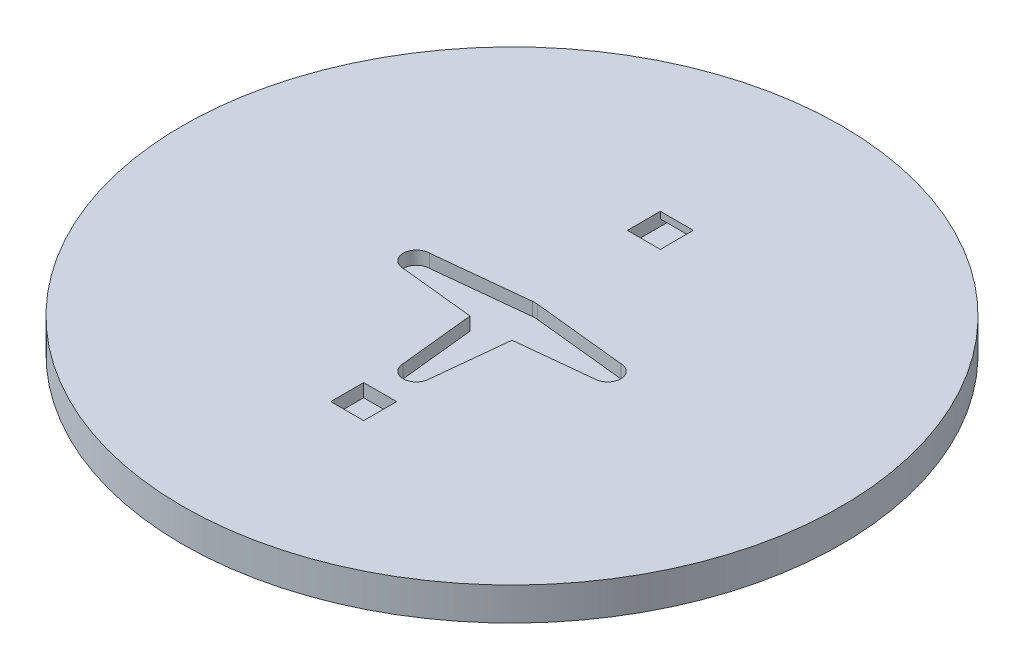
SolidWorks part; units mm, degrees
ref_plane "Front Plane" through (0, 0, 0) normal (0, 0, 1) x (1, 0, 0)
ref_plane "Top Plane" through (0, 0, 0) normal (0, 1, 0) x (1, 0, 0)
ref_plane "Right Plane" through (0, 0, 0) normal (1, 0, 0) x (0, 0, -1)
sketch "Sketch1" plane through (0, 0, 0) normal (0, 1, 0) x (1, 0, 0)
  circle A0 centre (0, 0) radius 50
  dimension "D1" = 100
extrude "Boss-Extrude1" add sketch "Sketch1" along normal blind 5
sketch "Sketch2" plane through (0, 5, 0) normal (0, 1, 0) x (1, 0, 0)
  line L1 (14.5, 2) -> (0.3647, 3.4809)
  line L2 (14.5, -2) -> (3.1854, -3.1854)
  line L3 (2, -14.5) -> (3.1854, -3.1854)
  line L4 (-2, -14.5) -> (-3.1854, -3.1854)
  line L5 (-14.5, -2) -> (-3.1854, -3.1854)
  line L6 (-14.5, 2) -> (-0.3647, 3.4809)
  arc A1 (14.5, -2) -> (14.5, 2) centre (14.5, 0) ccw
  arc A9 (-2, -14.5) -> (2, -14.5) centre (0, -14.5) ccw
  arc A10 (-14.5, 2) -> (-14.5, -2) centre (-14.5, 0) ccw
  arc A11 (0.3647, 3.4809) -> (-0.3647, 3.4809) centre (0, 0) ccw
  point P18 (0, 0)
  point P23 (0, 0)
  point P24 (0, 0)
  point P38 (0, 0)
  dimension "D2" = 4
  dimension "D3" = 3
extrude "Cut-Extrude1" cut sketch "Sketch2" against normal blind 2
sketch "Sketch3" plane through (0, 0, 0) normal (0, -1, 0) x (1, 0, 0)
  ellipse E0 centre (0, 0) end of major axis (0, -25) minor radius 7.5 (7.1837, 7.1837) -> (-7.1837, 7.1837) ccw
  ellipse E1 centre (0, 0) end of major axis (-25, 0) minor radius 7.5 (7.1837, -7.1837) -> (7.1837, 7.1837) ccw
  ellipse E2 centre (0, 0) end of major axis (0, -25) minor radius 7.5 (-7.1837, -7.1837) -> (7.1837, -7.1837) ccw
  ellipse E3 centre (0, 0) end of major axis (-25, 0) minor radius 7.5 (-7.1837, 7.1837) -> (-7.1837, -7.1837) ccw
  point P15 (0, 0)
extrude "Cut-Extrude3" cut sketch "Sketch3" against normal blind 2.5
sketch "Sketch4" plane through (0, 2.5, 0) normal (0, -1, 0) x (1, 0, 0)
  arc A0 (25, 0) -> (17.6777, 17.6777) centre (0, 0) ccw
  arc A1 (0, 25) -> (-17.6777, 17.6777) centre (0, 0) ccw
  arc A2 (-25, 0) -> (-17.6777, -17.6777) centre (0, 0) ccw
  arc A3 (0, -25) -> (17.6777, -17.6777) centre (0, 0) ccw
  ellipse E0 centre (0, 0) end of major axis (0, -25) minor radius 7.5 (6.0742, 14.6644) -> (0, 25) ccw
  ellipse E1 centre (0, 0) end of major axis (-25, 0) minor radius 7.5 (14.6644, -6.0742) -> (25, 0) ccw
  ellipse E2 centre (0, 0) end of major axis (0, -25) minor radius 7.5 (-6.0742, -14.6644) -> (0, -25) ccw
  ellipse E3 centre (0, 0) end of major axis (-25, 0) minor radius 7.5 (-14.6644, 6.0742) -> (-25, 0) ccw
  ellipse E4 centre (0, 0) end of major axis (-17.6777, -17.6777) minor radius 7.5 (17.6777, 17.6777) -> (6.0742, 14.6644) ccw
  ellipse E5 centre (0, 0) end of major axis (-17.6777, 17.6777) minor radius 7.5 (-17.6777, 17.6777) -> (-14.6644, 6.0742) ccw
  ellipse E6 centre (0, 0) end of major axis (-17.6777, -17.6777) minor radius 7.5 (-17.6777, -17.6777) -> (-6.0742, -14.6644) ccw
  ellipse E7 centre (0, 0) end of major axis (-17.6777, 17.6777) minor radius 7.5 (17.6777, -17.6777) -> (14.6644, -6.0742) ccw
  point P15 (0, 0)
  point P47 (0, 0)
extrude "Cut-Extrude4" cut sketch "Sketch4" along normal blind 1.5
sketch "Sketch5" plane through (0, 2.5, 0) normal (0, -1, 0) x (1, 0, 0)
  circle A0 centre (0, 0) radius 2.5
extrude "Boss-Extrude2" add sketch "Sketch5" along normal up to surface (2.5 mm away) up to face at (0, 0, 0)
sketch "Sketch6" plane through (0, 5, 0) normal (0, 1, 0) x (1, 0, 0)
  line L9 (-2.5, 25) -> (-2.5, 20)
  line L10 (2.5, -25) -> (-2.5, -25)
  line L18 (-2.5, 25) -> (2.5, 25)
  line L19 (2.5, -25) -> (2.5, -20)
  line L20 (2.5, -20) -> (-2.5, -20)
  line L21 (-2.5, -25) -> (-2.5, -20)
  line L22 (2.5, 25) -> (2.5, 20)
  line L23 (-2.5, 20) -> (2.5, 20)
  point P0 (0, -25)
  point P11 (0, 0)
  point P12 (0, 0)
  point P15 (0, 0)
  dimension "D1" = 2
extrude "Cut-Extrude7" cut sketch "Sketch6" against normal blind 2
sketch "Sketch8" plane through (0, 3, 0) normal (0, 1, 0) x (1, 0, 0)
  line L0 (-2.5, 25) -> (-2.5, 30)
  line L1 (2.5, -25) -> (-2.5, -25)
  line L2 (2.5, -25) -> (2.5, -30)
  line L3 (2.5, -30) -> (-2.5, -30)
  line L4 (-2.5, -25) -> (-2.5, -30)
  line L5 (-2.5, 25) -> (2.5, 25)
  line L6 (2.5, 25) -> (2.5, 30)
  line L7 (-2.5, 30) -> (2.5, 30)
  point P12 (0, 0)
  dimension "D1" = 5
  dimension "D2" = 5
  dimension "D3" = 2
extrude "Cut-Extrude8" cut sketch "Sketch8" along normal blind 1
